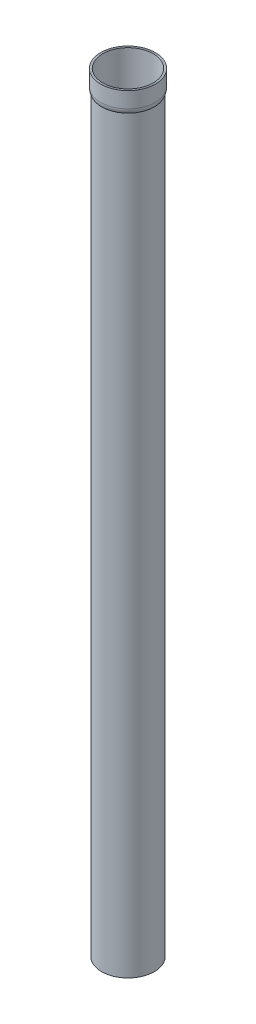
SolidWorks part; units mm, degrees
material "Plástico personalizado"
ref_plane "Plano frontal" through (0, 0, 0) normal (0, 0, 1) x (1, 0, 0)
ref_plane "Plano superior" through (0, 0, 0) normal (0, 1, 0) x (1, 0, 0)
ref_plane "Plano direito" through (0, 0, 0) normal (1, 0, 0) x (0, 0, -1)
sketch "Esboço1" plane through (0, 0, 0) normal (0, 1, 0) x (1, 0, 0)
  circle A0 centre (0, 0) radius 26
  circle A1 centre (0, 0) radius 25
extrude "Ressalto-extrusão1" add sketch "Esboço1" along normal blind 760 contours A0 | A1
sketch "Esboço2" plane through (0, 760, 0) normal (0, 1, 0) x (1, 0, 0)
  circle A1 centre (0, 0) radius 27
  circle A2 centre (0, 0) radius 26
extrude "Ressalto-extrusão2" add sketch "Esboço2" against normal blind 20 separate body
fillet "Filete2" radius 10 1 edges at (0, 740, 27) tangent propagation no
